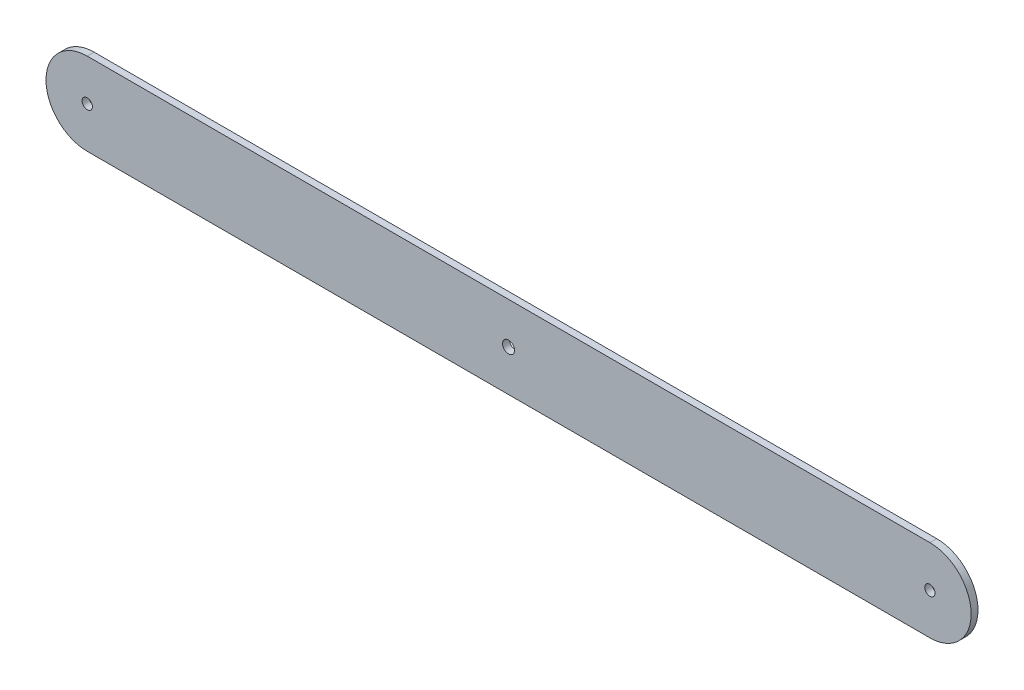
SolidWorks part; units mm, degrees
material "6061-T6 (SS)"
ref_plane "Front Plane" through (0, 0, 0) normal (0, 0, 1) x (1, 0, 0)
ref_plane "Top Plane" through (0, 0, 0) normal (0, 1, 0) x (1, 0, 0)
ref_plane "Right Plane" through (0, 0, 0) normal (1, 0, 0) x (0, 0, -1)
ref_axis "X" through (-88.99, 0, 0) along (1, 0, 0)
ref_axis "Y" through (0, 55, 0) along (0, -1, 0)
ref_axis "Z" through (0, 0, -88.99) along (0, 0, 1)
sketch "Sketch1" plane through (0, 0, 0) normal (0, 0, 1) x (1, 0, 0)
  line L0 (-122.6, 0) -> (122.6, 0) construction
  line L1 (-122.6, 12) -> (122.6, 12)
  line L2 (-122.6, -12) -> (122.6, -12)
  line L5 (-32.5, -12) -> (32.5, -12) construction
  arc A0 (-122.6, 12) -> (-122.6, -12) centre (-122.6, 0) ccw
  arc A1 (122.6, -12) -> (122.6, 12) centre (122.6, 0) ccw
  circle A2 centre (-122.6, 0) radius 1.5
  circle A3 centre (0, 0) radius 1.75
  circle A4 centre (122.6, 0) radius 1.5
  circle A5 centre (-122.6, 0) radius 1.5 construction
  circle A6 centre (0, 0) radius 1.75 construction
  point P2 (0, 0)
extrude "Boss-Extrude1" add sketch "Sketch1" along normal blind 2
